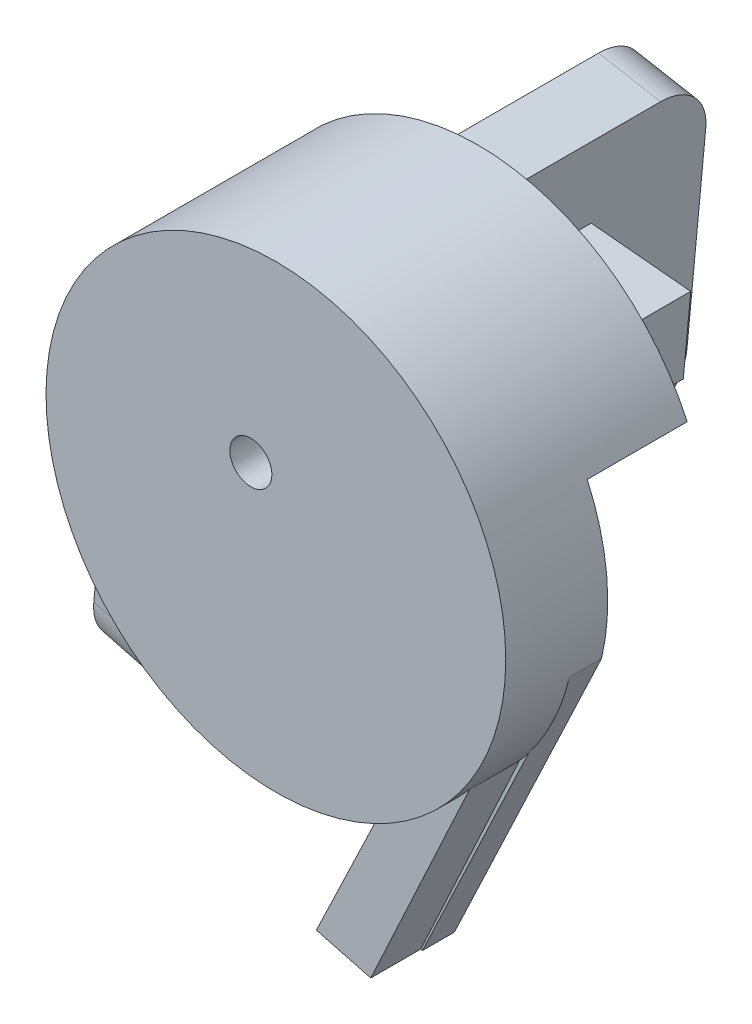
SolidWorks part; units mm, degrees
ref_plane "Front Plane" through (0, 0, 0) normal (0, 0, 1) x (1, 0, 0)
ref_plane "Top Plane" through (0, 0, 0) normal (0, 1, 0) x (1, 0, 0)
ref_plane "Right Plane" through (0, 0, 0) normal (1, 0, 0) x (0, 0, -1)
sketch "Sketch1" plane through (0, 0, 0) normal (0, 0, 1) x (1, 0, 0)
  line L0 (-16.7339, 0.7347) -> (-19.5437, -29.2653)
  line L1 (-19.5437, -29.2653) -> (1.9856, -34.8971)
  line L2 (1.9856, -34.8971) -> (14.8304, -7.786)
  line L3 (0.192, -0.8506) -> (14.8304, -7.786)
  line L4 (-16.7339, 0.7347) -> (0.192, -0.8506)
  line L5 (-22.9127, 2.0023) -> (-25.6907, -27.6574)
  line L6 (-25.6907, -27.6574) -> (7.6604, -36.3816)
  line L7 (7.6604, -36.3816) -> (22.3757, -5.3225)
  circle A0 centre (0, 0) radius 16.75
  circle A1 centre (0, 0) radius 23
  dimension "D2" = 33.5
  dimension "D12" = 0
  dimension "D13" = 46
  dimension "D1" = 0
  dimension "D3" = 16.75
  dimension "D4" = 16.75
  dimension "D5" = 0
  dimension "D6" = 30
  dimension "D7" = 90
  dimension "D10" = 90
  dimension "D11" = 30
  dimension "D14" = 23
  dimension "D15" = 23
  dimension "D16" = 180
  dimension "D17" = 180
  dimension "D19" = 160
extrude "Boss-Extrude3" add sketch "Sketch1" along normal blind 13.2 contours A1 L5 L6 L0 | A1 L0 A0 L2 L7 | A1 L2 L6 L7 region at (-18.0679, -6.6504, 0) region at (-21.9723, -18.3376, 0) region at (9.1273, -27.1046, 0)
sketch "Sketch2" plane through (0, 0, 0) normal (0, 0, -1) x (-1, 0, 0)
  line L0 (22.9127, 2.0023) -> (16.7206, 0.8761)
  line L1 (16.7206, 0.8761) -> (19.5437, -29.2653)
  line L2 (19.5437, -29.2653) -> (25.6907, -27.6574)
  line L3 (25.6907, -27.6574) -> (22.9127, 2.0023)
  line L4 (16.7339, 0.7347) -> (19.5437, -29.2653) construction
  line L5 (22.9127, 2.0023) -> (25.6907, -27.6574) construction
  line L7 (25.6907, -27.6574) -> (19.5437, -29.2653) construction
  point P4 (24.3017, -12.8275)
  point P11 (18.1388, -14.2653)
  dimension "D1" = 0
  dimension "D2" = 0
  dimension "D3" = 180
  dimension "D4" = 0
  dimension "D5" = 0
  dimension "D6" = 0
extrude "Boss-Extrude4" add sketch "Sketch2" along normal blind 40
sketch "Sketch3" plane through (0, 0, 13.2) normal (0, 0, 1) x (1, 0, 0)
  circle A0 centre (0, 0) radius 23
  arc A1 (14.8304, -7.786) -> (-16.7339, 0.7347) centre (0, 0) ccw construction
  dimension "D2" = 46
  dimension "D1" = 0
extrude "Boss-Extrude5" add sketch "Sketch3" along normal blind 7
sketch "Sketch4" plane through (0, 0, 20.2) normal (0, 0, 1) x (1, 0, 0)
  circle A0 centre (-2.506, 4.3267) radius 2.1017
  circle A2 centre (0, 0) radius 23 construction
  dimension "D1" = 5
extrude "Cut-Extrude1" cut sketch "Sketch4" against normal blind 10
sketch "Sketch6" plane through (0, 0, 0) normal (0, 0, -1) x (-1, 0, 0)
  line L1 (-26.1892, 9.4902) -> (-0.4743, 9.4902)
  line L2 (-26.1892, 9.4902) -> (-26.1892, -44.4369)
  line L3 (-26.1892, -44.4369) -> (-0.4743, -44.4369)
  line L4 (-0.4743, 9.4902) -> (-0.4743, -44.4369)
extrude "Cut-Extrude2" cut sketch "Sketch6" against normal blind 10
sketch "Sketch7" plane through (0, 0, 13.2) normal (0, 0, 1) x (1, 0, 0)
  line L0 (2.0506, -34.9141) -> (7.4943, -36.3381)
  line L1 (7.4943, -36.3381) -> (17.7899, -14.1801)
  line L2 (17.7899, -14.1801) -> (12.5045, -13.1112)
  line L3 (12.5045, -13.1112) -> (2.0506, -34.9141)
  line L4 (1.9856, -34.8971) -> (7.6604, -36.3816) construction
  arc M1 (18.2907, -13.9445) -> (8.3693, -21.4232) centre (0, 0) cw
  line M3 (1.9856, -34.8971) -> (7.6604, -36.3816)
  dimension "D1" = 180
  dimension "D2" = 0
extrude "Boss-Extrude6" add sketch "Sketch7" along normal blind 5 contours L3 L1 M1 M3 region at (8.9193, -27.284, 13.2)
sketch "Sketch8" plane through (-16.6566, 1.5601, 0) normal (0.9956, -0.0933, 0) x (0, 0, -1)
  line L0 (-13.2, -0.829) -> (-13.2, -15.7837) construction
  line L1 (28.8, -8.5) -> (13.8, -8.5)
  line L2 (28.8, -8.5) -> (28.8, -16.5)
  line L3 (28.8, -16.5) -> (13.8, -16.5)
  line L4 (13.8, -8.5) -> (13.8, -16.5)
  line L5 (0, 23) -> (-20.2, 23) construction
  line L6 (14.6914, -16.5) -> (10.6914, -16.5)
  line L7 (10.6914, -16.5) -> (13.8, -8.5)
  line L8 (11.5362, -16.5) -> (11.3479, -14.8105)
  dimension "D1" = 27
  dimension "D2" = 8
  dimension "D3" = 31.5
  dimension "D4" = 0
  dimension "D5" = 0
  dimension "D6" = 4
  dimension "D7" = 180
  dimension "D8" = 0
  dimension "D9" = 0
  dimension "D10" = 1.7
  dimension "D11" = 15
extrude "Boss-Extrude10" add sketch "Sketch8" along normal blind 10 contours L1 L4 L3 L2 | L8 L6 L4 L7 region at (-17.8222, -10.8854, -21.3) region at (-17.9346, -12.0855, -12.8595)
fillet "Fillet4" radius 3 1 edges at (-12.471, -7.3691, -13.8) type face fillet first side face at (-12.471, -7.3691, -21.3) second side face at (-12.7653, -10.5106, -12.574)
sketch "Sketch10" plane through (-6.7001, 0.6275, 0) normal (0.9956, -0.0933, 0) x (0, 0, -1)
  circle A0 centre (21.36, -12.5805) radius 1.4
  dimension "D1" = 2.8
extrude "Cut-Extrude4" cut sketch "Sketch10" against normal blind 10
sketch "Sketch11" plane through (-22.8993, 2.1448, 0) normal (-0.9956, 0.0933, 0) x (0, 0, 1)
  text T0 "GIAU-QUANG" font "Century Gothic" height in points 15
extrude "Cut-Extrude5" cut sketch "Sketch11" against normal blind 5
fillet "Fillet5" radius 5 1 edges at (-22.6172, -28.4613, -40) type face fillet first side face at (-21.2169, -13.5111, -40) second side face at (-22.6172, -28.4613, -13.4)
fillet "Fillet6" radius 5 1 edges at (-19.8167, 1.4392, -40) type face fillet first side face at (-19.1987, 1.3268, -16) second side face at (-20.9807, -10.9888, -40)
fillet "Fillet7" radius 5 1 edges at (-22.6172, -28.4613, 13.2) type face fillet first side face at (-21.8197, -11.5417, 13.2) second side face at (-22.6172, -28.4613, -10.9)
